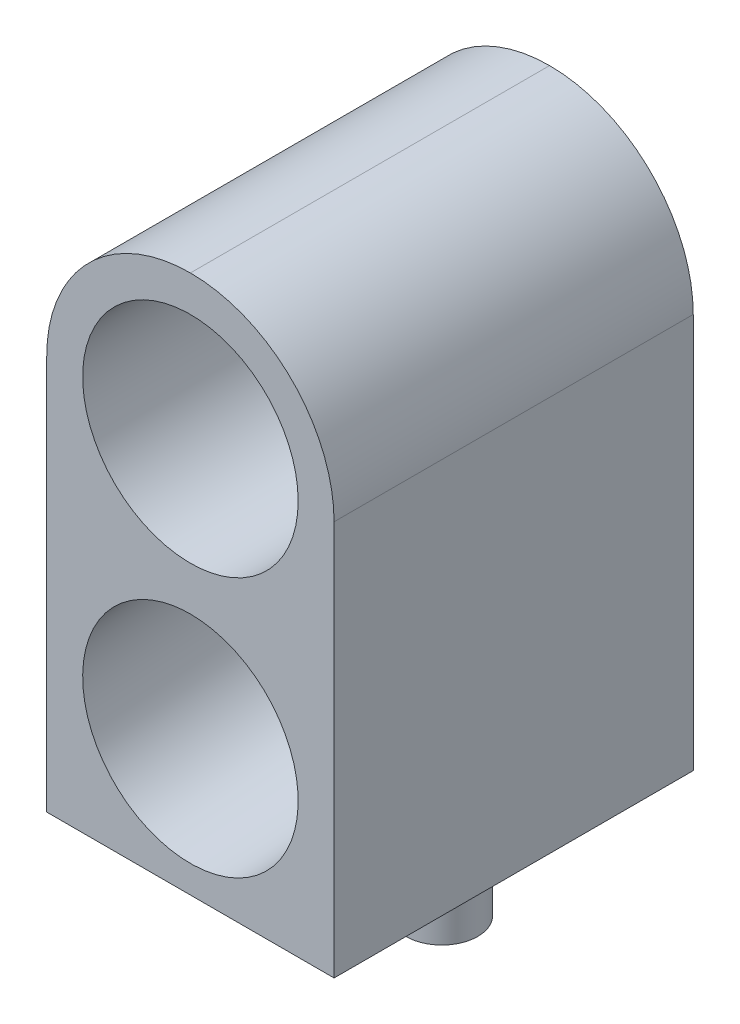
SolidWorks part; units mm, degrees
ref_plane "Płaszczyzna przednia" through (0, 0, 0) normal (0, 0, 1) x (1, 0, 0)
ref_plane "Płaszczyzna górna" through (0, 0, 0) normal (0, 1, 0) x (1, 0, 0)
ref_plane "Płaszczyzna prawa" through (0, 0, 0) normal (1, 0, 0) x (0, 0, -1)
sketch "Szkic1" plane through (0, 0, 0) normal (0, 0, 1) x (1, 0, 0)
  line L1 (-4, -7.5) -> (4, -7.5)
  line L2 (-4, -7.5) -> (-4, 7.5)
  line L3 (-4, 7.5) -> (4, 7.5)
  line L4 (4, -7.5) -> (4, 7.5)
  line L5 (-4, -7.5) -> (4, 7.5) construction
  line L6 (-4, 7.5) -> (4, -7.5) construction
  point P0 (0, 0)
  dimension "D1" = 8
  dimension "D2" = 15
extrude "Dodanie-wyciągnięcie1" add sketch "Szkic1" along normal blind 10
fillet "Zaokrąglenie1" radius 4 2 edges at (4, 7.5, 5) (-4, 7.5, 5)
sketch "Szkic2" plane through (0, -7.5, 0) normal (0, -1, 0) x (1, 0, 0)
  line L0 (-4, 0) -> (4, 0) construction
  line L2 (-4, 10) -> (-4, 0) construction
  line L3 (4, 10) -> (4, 0) construction
  circle A0 centre (-2, 5) radius 1
  circle A1 centre (2, 5) radius 1
  dimension "D1" = 2
  dimension "D2" = 2
  dimension "D3" = 5
  dimension "D4" = 5
  dimension "D5" = 2
  dimension "D6" = 2
extrude "Dodanie-wyciągnięcie2" add sketch "Szkic2" along normal blind 2
sketch "Szkic4" plane through (0, 0, 10) normal (0, 0, 1) x (1, 0, 0)
  line L0 (-4, -7.5) -> (4, -7.5) construction
  circle A0 centre (0, 3.5) radius 3
  dimension "D1" = 6
  dimension "D4" = 11
extrude "Wytnij-wyciągnięcie1" cut sketch "Szkic4" against normal blind 15
sketch "Szkic7" plane through (0, 0, 0) normal (1, 0, 0) x (0, 0, -1)
  line L0 (4.1879, 3.5) -> (-15.8121, 3.5) construction
  line L1 (5.3494, -2.6574) -> (-14.8572, -4.0704) construction
  line L2 (-6.7, 3.5) -> (-6.7, -3.5) construction
  line L3 (-10, -7.5) -> (-10, 3.5) construction
  line L5 (-10, -7.5) -> (0, -7.5) construction
  dimension "D1" = 4
  dimension "D2" = 3.3
  dimension "D3" = 7
  dimension "D4" = 4
ref_plane "Płaszczyzna1" through (0, -2.6574, -5.3494) normal (0, -0.0698, 0.9976) x (1, 0, 0)
sketch "Szkic9" plane through (0, -2.6574, -5.3494) normal (0, -0.0698, 0.9976) x (1, 0, 0)
  circle A0 centre (0, 0) radius 3
extrude "Wytnij-wyciągnięcie2" cut sketch "Szkic9" along normal blind 25
